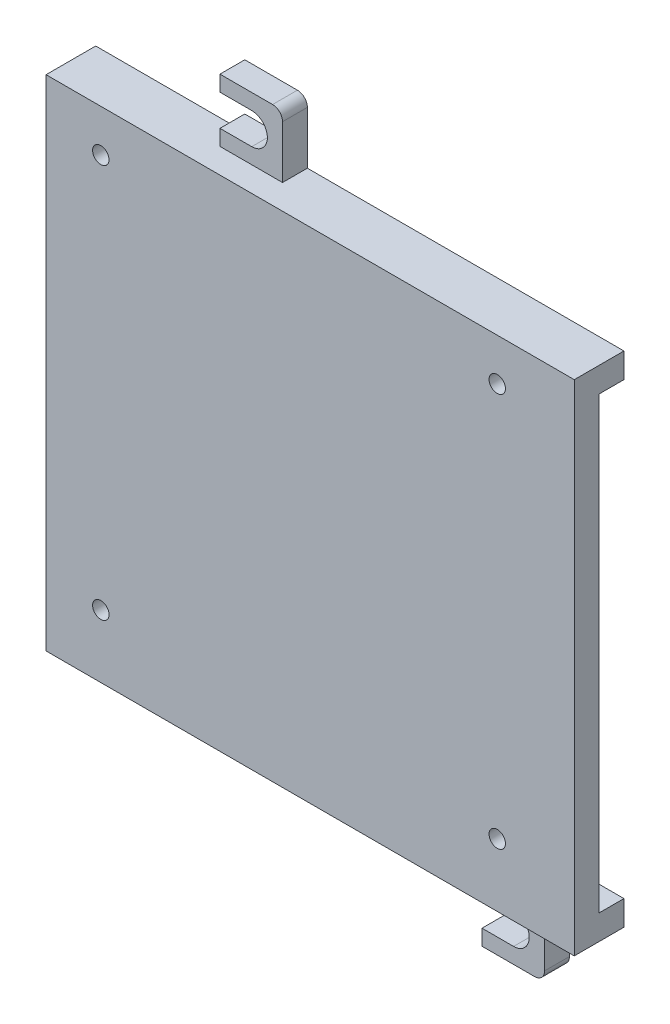
SolidWorks part; units mm, degrees
material "Custom Plastic"
ref_plane "X-Y Datum" through (0, 0, 0) normal (0, 0, 1) x (1, 0, 0)
ref_plane "X-Z Datum" through (0, 0, 0) normal (0, 1, 0) x (1, 0, 0)
ref_plane "Y-Z Datum" through (0, 0, 0) normal (1, 0, 0) x (0, 0, -1)
sketch "Sketch1" plane through (0, 0, -64.8744) normal (0, 0, -1) x (-1, 0, 0)
  line L0 (-199.1695, -111.5445) -> (-199.1695, -82.0518)
  line L1 (-199.1695, -130.2123) -> (-199.1695, -20.4133) construction
  line L3 (-181.1162, -23.6402) -> (-179.9457, -24.367) construction
  line L5 (-199.1695, -17.8733) -> (-64.1381, -17.8733)
  line L6 (-199.1695, -17.8733) -> (-199.1695, -132.7523)
  line L7 (-199.1695, -132.7523) -> (-64.1381, -132.7523)
  line L8 (-64.1381, -17.8733) -> (-64.1381, -132.7523)
  circle A0 centre (-179.4845, -22.3183) radius 2.1
  circle A1 centre (-78.1385, -22.3183) radius 2.1
  circle A2 centre (-78.1385, -123.0293) radius 2.1
  circle A3 centre (-179.4845, -123.0293) radius 2.1
  point P24 (-81.017, -75.3128)
  dimension "D2" = 114.879
  dimension "D3" = 135.0314
extrude "Boss-Extrude1" add sketch "Sketch1" along normal blind 6.35 contours L8 L5 L6 L0 L7 A3 A2 A1 A0 region at (131.664, -75.3223, -64.8744)
fillet "Fillet1" [suppressed] radius 2.54
sketch "Sketch4" plane through (0, 0, -71.2244) normal (0, 0, -1) x (-1, 0, 0)
  line L0 (-199.1695, -11.5233) -> (-199.1695, -17.8733)
  line L1 (-199.1695, -132.7523) -> (-199.1695, -139.1023)
  line L4 (-199.1695, -17.8733) -> (-199.1695, -132.7523)
  line L7 (-199.1695, -11.5233) -> (-64.1381, -11.5233)
  line L9 (-199.1695, -17.8733) -> (-64.1381, -17.8733)
  line L10 (-64.1381, -11.5233) -> (-64.1381, -17.8733)
  line L11 (-199.1695, -139.1023) -> (-64.1381, -139.1023)
  line L13 (-199.1695, -132.7523) -> (-64.1381, -132.7523)
  line L14 (-64.1381, -139.1023) -> (-64.1381, -132.7523)
  line M10 (-199.1695, -132.7523) -> (-64.1381, -132.7523)
  line M14 (-64.1381, -17.8733) -> (-199.1695, -17.8733)
  dimension "D2" = 6.35
extrude "Boss-Extrude2" add sketch "Sketch4" along normal blind 6.35 and the other way blind 6.35 contours L11 L14 L1 M10 | L10 L7 L0 M14 region at (131.6538, -14.6983, -71.2244) region at (131.6538, -135.9273, -71.2244)
sketch "Sketch5" plane through (0, 0, -77.5744) normal (0, 0, -1) x (-1, 0, 0)
  line L0 (-118.2381, -11.5233) -> (-118.2381, 4.4767)
  line L1 (-110.3641, 0.4767) -> (-102.2381, 0.4767)
  line L2 (-118.2381, 4.4767) -> (-102.2381, 4.4767)
  line L8 (-185.2348, -139.1023) -> (-185.2348, -155.1023)
  line L9 (-110.3641, -7.5233) -> (-102.2381, -7.5233)
  line L10 (-185.2348, -155.1023) -> (-169.2348, -155.1023)
  line L11 (-169.2348, -155.1023) -> (-169.2348, -139.1023)
  line L18 (-102.2381, 4.4767) -> (-102.2381, -11.5233)
  line L19 (-177.31, -143.1023) -> (-169.2348, -143.1023)
  line L20 (-199.1695, -132.7523) -> (-199.1695, -139.1023) construction
  line L21 (-177.31, -151.1023) -> (-169.2348, -151.1023)
  line L23 (-64.1381, -11.5233) -> (-64.1381, -139.1023) construction
  line L24 (-185.2348, -139.1023) -> (-169.2348, -139.1023)
  line L25 (-118.2381, -11.5233) -> (-102.2381, -11.5233)
  arc A2 (-110.3641, 0.4767) -> (-110.3641, -7.5233) centre (-110.3641, -3.5233) ccw
  arc A3 (-177.31, -143.1023) -> (-177.31, -151.1023) centre (-177.31, -147.1023) ccw
  dimension "D1" = 16
  dimension "D5" = 13.9348
  dimension "D2" = 16
  dimension "D3" = 7.874
  dimension "D4" = 8
  dimension "D6" = 16
  dimension "D7" = 16
  dimension "D8" = 38.1
  dimension "D9" = 7.9248
extrude "Boss-Extrude3" add sketch "Sketch5" against normal blind 6.35 contours L18 L2 L0 | A3 L11 L8 L10 region at (118.0118, -3.5233, -77.5744) region at (177.2348, -139.3286, -77.5744)
fillet "Fillet2" radius 2.54 1 edges at (118.2381, 4.4767, -74.3994)
fillet "Fillet3" radius 2.54 1 edges at (185.2348, -155.1023, -74.3994)
